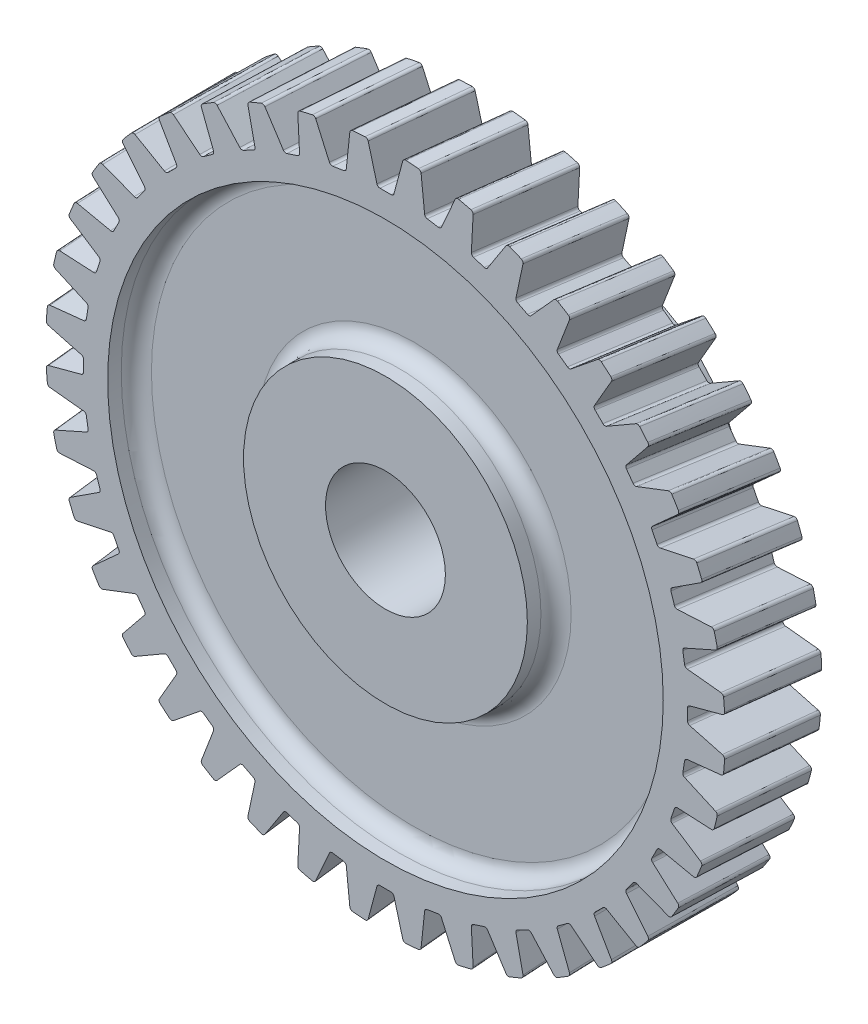
SolidWorks part; units mm, degrees
ref_plane "Front Plane" through (0, 0, 0) normal (0, 0, 1) x (1, 0, 0)
ref_plane "Top Plane" through (0, 0, 0) normal (0, 1, 0) x (1, 0, 0)
ref_plane "Right Plane" through (0, 0, 0) normal (1, 0, 0) x (0, 0, -1)
sketch "Sketch2" plane through (0, 0, 0) normal (1, 0, 0) x (0, 0, -1)
  line L0 (0, 0) -> (0, 22.5) construction
  line L1 (11, 3.9688) -> (-3.2, 3.9687)
  line L2 (-3.2, 3.9687) -> (-3.2, 9.4)
  line L3 (-3.2, 9.4) -> (-1.3, 9.4)
  line L4 (-1.3, 9.4) -> (-1.3, 18.4)
  line L5 (-1.3, 18.4) -> (-3.2, 18.4)
  line L6 (-3.2, 18.4) -> (-3.2, 22.5)
  line L7 (-3.2, 22.5) -> (3.2, 22.5)
  line L8 (3.2, 18.4) -> (3.2, 22.5)
  line L9 (1.3, 18.4) -> (3.2, 18.4)
  line L10 (1.3, 9.4) -> (1.3, 18.4)
  line L11 (3.2, 9.4) -> (1.3, 9.4)
  line L12 (3.2, 9.4) -> (11, 9.4)
  line L13 (11, 9.4) -> (11, 3.9688)
  line L14 (0, 0) -> (14.174, 0) construction
  dimension "D1" = 14.2
  dimension "D2" = 3.2
  dimension "D3" = 4.5
  dimension "D4" = 7.9375
  dimension "D5" = 9.4
  dimension "D6" = 9
  dimension "D7" = 22.5
  dimension "D8" = 6.4
revolve "Revolve1" add sketch "Sketch2" angle 360 about L14
fillet "Fillet1" radius 1 4 edges at (18.4, 0, 1.3) (9.4, 0, 1.3) (9.4, 0, -1.3) (18.4, 0, -1.3)
sketch "Sketch3" plane through (0, 0, 3.2) normal (0, 0, 1) x (1, 0, 0)
  line L0 (0, 22.6922) -> (0, 20) construction
  line L1 (-0.525, 20) -> (0.525, 20)
  line L2 (0.525, 20) -> (1.2464, 22.6922)
  line L3 (1.2464, 22.6922) -> (-1.2464, 22.6922)
  line L4 (-0.525, 20) -> (-1.2464, 22.6922)
  dimension "D1" = 20
  dimension "D2" = 1.05
  dimension "D3" = 15
sketch "Sketch4" plane through (0, 0, 0) normal (0, 1, 0) x (1, 0, 0)
  line L0 (0, -3.2) -> (0.691, 3.2)
  line L1 (1.2464, -3.2) -> (-1.2464, -3.2) construction
  line L2 (22.5, 3.2) -> (-22.5, 3.2) construction
sweep "Cut-Sweep1" cut profiles "Sketch3" path "Sketch4"
pattern_circular "CirPattern1" count 40 over 360 about axis through (0, 0, 3.2) along (0, 0, 1) of "Cut-Sweep1"
fillet "Fillet2" radius 0.2 160 edges at (1.526, 22.4482, 0.0047) (0.8705, 20, 0) (-0.8445, 22.4841, -0.0056) (-2.0045, 22.4105, 0.0047) (-2.2689, 19.8899, 0) (-3.306, 19.7257, 0) (-4.3514, 22.0752, -0.0056) (-5.4856, 21.8211, 0.0047) (-5.3525, 19.2901, 0) (-6.3511, 18.9657, 0) (-7.7512, 21.1227, -0.0056) (-8.8316, 20.6943, 0.0047) (-8.3042, 18.2153, 0) (-9.2398, 17.7386, 0) (-10.9601, 19.6501, -0.0056) (-11.9602, 19.0579, 0.0047) (-11.0515, 16.692, 0) (-11.9009, 16.0748, 0) (-13.8991, 17.6936, -0.0056) (-14.7943, 16.9523, 0.0047) (-13.5266, 14.7577, 0) (-14.2691, 14.0152, 0) (-16.4959, 15.3015, -0.0056) (-17.264, 14.4292, 0.0047) (-15.6687, 12.4599, 0) (-16.2859, 11.6105, 0) (-18.6865, 12.5326, -0.0056) (-19.3087, 11.5509, 0.0047) (-17.4249, 9.8554, 0) (-17.9016, 8.9199, 0) (-20.4169, 9.4551, -0.0056) (-20.878, 8.3882, 0.0047) (-18.7521, 7.0082, 0) (-19.0766, 6.0096, 0) (-21.6447, 6.1448, -0.0056) (-21.9331, 5.0188, 0.0047) (-19.6176, 3.9885, 0) (-19.7818, 2.9514, 0) (-22.3394, 2.6832, -0.0056) (-22.4482, 1.526, 0.0047) (-20, 0.8705, 0) (-20, -0.1795, 0) (-22.4841, -0.8445, -0.0056) (-22.4105, -2.0045, 0.0047) (-19.8899, -2.2689, 0) (-19.7257, -3.306, 0) (-22.0752, -4.3514, -0.0056) (-21.8211, -5.4856, 0.0047) (-19.2901, -5.3525, 0) (-18.9657, -6.3511, 0) (-21.1227, -7.7512, -0.0056) (-20.6943, -8.8316, 0.0047) (-18.2153, -8.3042, 0) (-17.7386, -9.2398, 0) (-19.6501, -10.9601, -0.0056) (-19.0579, -11.9602, 0.0047) (-16.692, -11.0515, 0) (-16.0748, -11.9009, 0) (-17.6936, -13.8991, -0.0056) (-16.9523, -14.7943, 0.0047) (-14.7577, -13.5266, 0) (-14.0152, -14.2691, 0) (-15.3015, -16.4959, -0.0056) (-14.4292, -17.264, 0.0047) (-12.4599, -15.6687, 0) (-11.6105, -16.2859, 0) (-12.5326, -18.6865, -0.0056) (-11.5509, -19.3087, 0.0047) (-9.8554, -17.4249, 0) (-8.9199, -17.9016, 0) (-9.4551, -20.4169, -0.0056) (-8.3882, -20.878, 0.0047) (-7.0082, -18.7521, 0) (-6.0096, -19.0766, 0) (-6.1448, -21.6447, -0.0056) (-5.0188, -21.9331, 0.0047) (-3.9885, -19.6176, 0) (-2.9514, -19.7818, 0) (-2.6832, -22.3394, -0.0056) (-1.526, -22.4482, 0.0047) (-0.8705, -20, 0) (0.1795, -20, 0) (0.8445, -22.4841, -0.0056) (2.0045, -22.4105, 0.0047) (2.2689, -19.8899, 0) (3.306, -19.7257, 0) (4.3514, -22.0752, -0.0056) (5.4856, -21.8211, 0.0047) (5.3525, -19.2901, 0) (6.3511, -18.9657, 0) (7.7512, -21.1227, -0.0056) (8.8316, -20.6943, 0.0047) (8.3042, -18.2153, 0) (9.2398, -17.7386, 0) (10.9601, -19.6501, -0.0056) (11.9602, -19.0579, 0.0047) (11.0515, -16.692, 0) (11.9009, -16.0748, 0) (13.8991, -17.6936, -0.0056) (14.7943, -16.9523, 0.0047) (13.5266, -14.7577, 0) (14.2691, -14.0152, 0) (16.4959, -15.3015, -0.0056) (17.264, -14.4292, 0.0047) (15.6687, -12.4599, 0) (16.2859, -11.6105, 0) (18.6865, -12.5326, -0.0056) (19.3087, -11.5509, 0.0047) (17.4249, -9.8554, 0) (17.9016, -8.9199, 0) (20.4169, -9.4551, -0.0056) (20.878, -8.3882, 0.0047) (18.7521, -7.0082, 0) (19.0766, -6.0096, 0) (21.6447, -6.1448, -0.0056) (21.9331, -5.0188, 0.0047) (19.6176, -3.9885, 0) (19.7818, -2.9514, 0) (22.3394, -2.6832, -0.0056) (22.4482, -1.526, 0.0047) (20, -0.8705, 0) (20, 0.1795, 0) (22.4841, 0.8445, -0.0056) (22.4105, 2.0045, 0.0047) (19.8899, 2.2689, 0) (19.7257, 3.306, 0) (22.0752, 4.3514, -0.0056) (21.8211, 5.4856, 0.0047) (19.2901, 5.3525, 0) (18.9657, 6.3511, 0) (21.1227, 7.7512, -0.0056) (20.6943, 8.8316, 0.0047) (18.2153, 8.3042, 0) (17.7386, 9.2398, 0) (19.6501, 10.9601, -0.0056) (19.0579, 11.9602, 0.0047) (16.692, 11.0515, 0) (16.0748, 11.9009, 0) (17.6936, 13.8991, -0.0056) (16.9523, 14.7943, 0.0047) (14.7577, 13.5266, 0) (14.0152, 14.2691, 0) (15.3015, 16.4959, -0.0056) (14.4292, 17.264, 0.0047) (12.4599, 15.6687, 0) (11.6105, 16.2859, 0) (12.5326, 18.6865, -0.0056) (11.5509, 19.3087, 0.0047) (9.8554, 17.4249, 0) (8.9199, 17.9016, 0) (9.4551, 20.4169, -0.0056) (8.3882, 20.878, 0.0047) (7.0082, 18.7521, 0) (6.0096, 19.0766, 0) (6.1448, 21.6447, -0.0056) (5.0188, 21.9331, 0.0047) (3.9885, 19.6176, 0) (2.9514, 19.7818, 0) (2.6832, 22.3394, -0.0056) (-0.1795, 20, 0)
ref_axis "gear axis" through (0, 0, -11) along (0, 0, 1)
